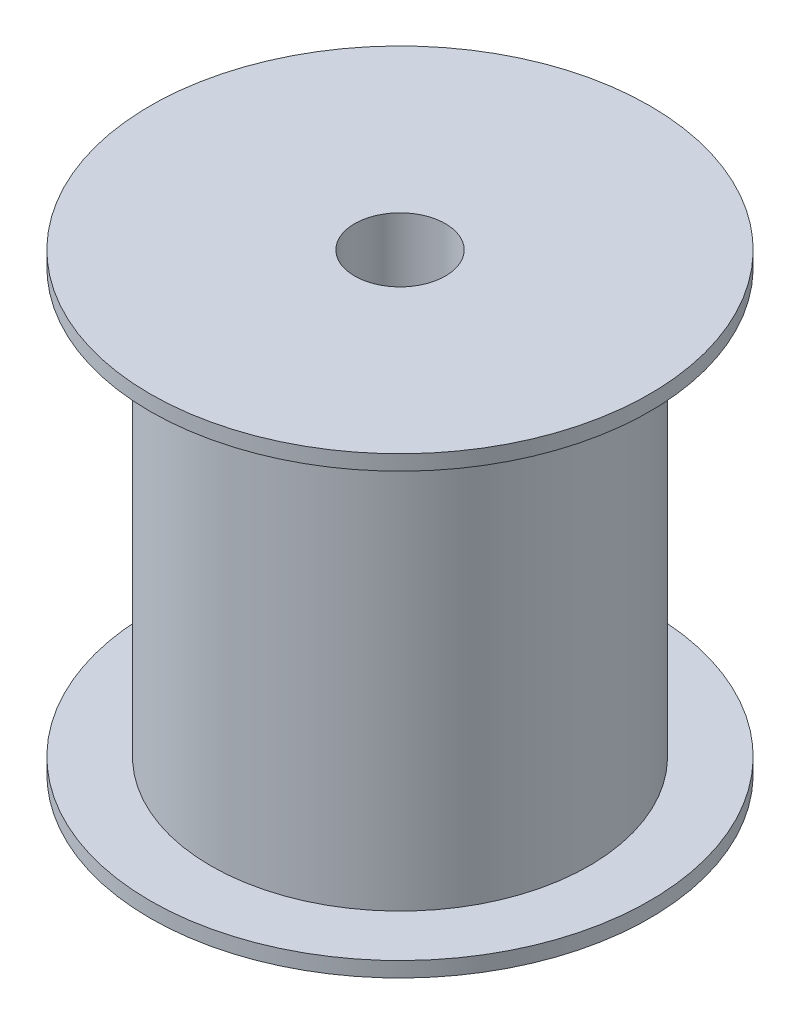
SolidWorks part; units mm, degrees
ref_plane "Plan de face" through (0, 0, 0) normal (0, 0, 1) x (1, 0, 0)
ref_plane "Plan de dessus" through (0, 0, 0) normal (0, 1, 0) x (1, 0, 0)
ref_plane "Plan de droite" through (0, 0, 0) normal (1, 0, 0) x (0, 0, -1)
sketch "Esquisse1" plane through (0, 0, 0) normal (0, 1, 0) x (1, 0, 0)
  circle A0 centre (0, 0) radius 16.5
  circle A1 centre (0, 0) radius 12.5
  dimension "D1" = 4
  dimension "D2" = 25
extrude "Boss.-Extru.1" add sketch "Esquisse1" along normal blind 30 contours A1 region at (0, 0, 0)
extrude "Boss.-Extru.2" add sketch "Esquisse1<3>" along normal blind 1
sketch "Esquisse1<3>" plane through (0, 0, 0) normal (0, 1, 0) x (1, 0, 0) same geometry as "Esquisse1"
sketch "Esquisse2" plane through (0, 30, 0) normal (0, 1, 0) x (1, 0, 0)
  circle A0 centre (0, 0) radius 16.5
  circle A1 centre (0, 0) radius 16.5 construction
extrude "Boss.-Extru.3" add sketch "Esquisse2" against normal blind 1
sketch "Esquisse3" plane through (0, 0, 0) normal (0, -1, 0) x (1, 0, 0)
  circle A0 centre (0, 0) radius 1.1525
  dimension "D1" = 2.305
sketch "Esquisse4" plane through (0, 30, 0) normal (0, 1, 0) x (1, 0, 0)
  circle A0 centre (0, 0) radius 3
  dimension "D1" = 6
extrude "Enlèv. mat.-Extru.1" cut sketch "Esquisse3" against normal blind 6 contours A0
extrude "Enlèv. mat.-Extru.2" cut sketch "Esquisse4" against normal blind 5 contours A0
sketch3d "Esquisse3D1"
  line L0 (0, 14.9803, 0) -> (0, 29.9605, 0) construction
  line L3 (0, 14.9803, 0) -> (0, 0, 0) construction
  line L4 (0, 25, 0) -> (0, 30, 0) construction
  line L5 (0, 29, 0) -> (0, 30, 0) construction
